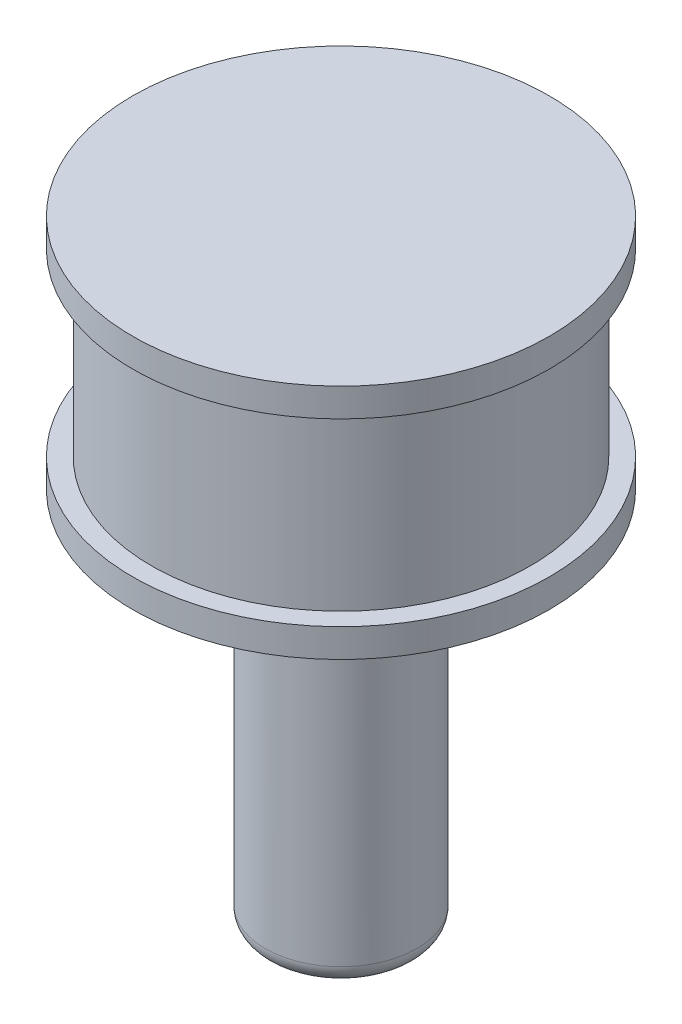
SolidWorks part; units mm, degrees
ref_plane "Front Plane" through (0, 0, 0) normal (0, 0, 1) x (1, 0, 0)
ref_plane "Top Plane" through (0, 0, 0) normal (0, 1, 0) x (1, 0, 0)
ref_plane "Right Plane" through (0, 0, 0) normal (1, 0, 0) x (0, 0, -1)
sketch "Sketch1" plane through (0, 0, 0) normal (0, 0, 1) x (1, 0, 0)
  line L2 (-4, -20) -> (-4, 0)
  line L3 (-4, 0) -> (-11, 0)
  line L4 (-11, 0) -> (-11, 1.5)
  line L5 (-11, 1.5) -> (-10, 1.5)
  line L6 (-10, 1.5) -> (-10, 11)
  line L7 (-10, 11) -> (-11, 11)
  line L8 (-11, 11) -> (-11, 12.5)
  line L9 (-11, 12.5) -> (0, 12.5)
  line L10 (0, 12.5) -> (0, -20)
  line L11 (0, -20) -> (-4, -20)
  dimension "D1" = 4
  dimension "D2" = 1
  dimension "D3" = 20
  dimension "D4" = 1.5
  dimension "D7" = 12.5
  dimension "D8" = 10
revolve "Revolve1" add sketch "Sketch1" angle 360 about L10
fillet "Fillet1" radius 1 1 edges at (-4, -20, 0)
